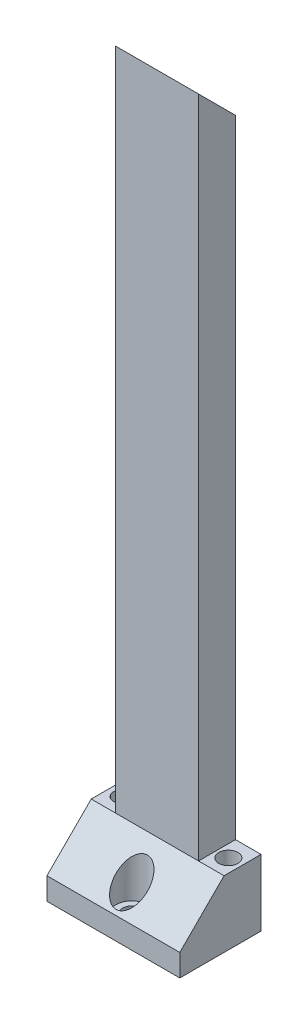
SolidWorks part; units mm, degrees
ref_plane "Front Plane" through (0, 0, 0) normal (0, 0, 1) x (1, 0, 0)
ref_plane "Top Plane" through (0, 0, 0) normal (0, 1, 0) x (1, 0, 0)
ref_plane "Right Plane" through (0, 0, 0) normal (1, 0, 0) x (0, 0, -1)
sketch "Sketch1" plane through (0, 0, 0) normal (0, 1, 0) x (1, 0, 0)
  line L0 (-2, 8.9269) -> (-2, -9.4231) construction
  line L1 (-17, 8.9269) -> (13, 8.9269)
  line L2 (-17, 8.9269) -> (-17, -9.4231)
  line L3 (-17, -9.4231) -> (13, -9.4231)
  line L4 (13, 8.9269) -> (13, -9.4231)
  line L5 (-17, 4.5423) -> (13, 4.5423)
  circle A0 centre (10, 4.5423) radius 2.1584
  circle A1 centre (-14, 4.5423) radius 1.9195
  circle A2 centre (-2, -5.2684) radius 2.1376
  point P9 (-2, 8.9269)
  point P12 (0, 0)
  dimension "D1" = 30
  dimension "D2" = 13
  dimension "D3" = 18.35
  dimension "D4" = 12
  dimension "D5" = 12
  dimension "D6" = 15.5
extrude "Boss-Extrude1" add sketch "Sketch1" along normal blind 15 contours L1 L0 L5 A0 L4 | L0 L1 L2 L5 A1 | L0 L5 A1 L2 L3 A2 | L5 L0 A2 L3 L4 A0 region at (4.9366, 0, -6.8944) region at (-9.0658, 0, -6.8675) region at (5.5738, 0, 2.564) region at (-9.6083, 0, 2.5188)
chamfer "Chamfer1" distance 10 angle 45 1 edges at (-2, 15, 9.4231)
ref_plane "Plane1" through (0, 15, 0) normal (0, 1, 0) x (1, 0, 0)
sketch "Sketch2" plane through (0, 15, 0) normal (0, 1, 0) x (1, 0, 0)
  circle A0 centre (-2, -5.2684) radius 3.5447
extrude "Cut-Extrude1" cut sketch "Sketch2" against normal blind 12
sketch "Sketch3" plane through (0, 15, 0) normal (0, 1, 0) x (1, 0, 0)
  line L0 (7.8416, 4.5423) -> (7.8416, 0.5769) construction
  line L1 (-17, 0.5769) -> (13, 0.5769) construction
  line L2 (-12.0805, 4.5423) -> (-12.0805, 0.5769) construction
  line L3 (-17, 8.9269) -> (13, 8.9269) construction
  line L4 (-11.5265, 0.5769) -> (7.2327, 0.5769)
  line L5 (-11.5265, 0.5769) -> (-11.5265, 8.9269)
  line L6 (-11.5265, 8.9269) -> (7.2327, 8.9269)
  line L7 (7.2327, 0.5769) -> (7.2327, 8.9269)
  circle A0 centre (10, 4.5423) radius 2.1584 construction
  circle A1 centre (-14, 4.5423) radius 1.9195 construction
extrude "Boss-Extrude2" add sketch "Sketch3" along normal blind 150
sketch "Sketch4" plane through (7.2327, 0, 0) normal (1, 0, 0) x (0, 0, -1)
  line L0 (0.5769, 165) -> (8.9269, 156.65)
  line L1 (8.9269, 165) -> (8.9269, 15) construction
  line L2 (8.9269, 156.65) -> (8.9269, 165)
  line L3 (8.9269, 165) -> (0.5769, 165)
extrude "Cut-Extrude2" cut sketch "Sketch4" against normal blind 150
sketch "Sketch5" plane through (0, 82.7885, -82.7885) normal (0, 0.7071, -0.7071) x (1, 0, 0)
  line L1 (3.7365, -112.0212) -> (-8.9793, -112.0212)
  line L2 (3.7365, -112.0212) -> (3.7365, -108.4294)
  line L3 (3.7365, -108.4294) -> (-8.9793, -108.4294)
  line L4 (-8.9793, -112.0212) -> (-8.9793, -108.4294)
extrude "Cut-Extrude3" cut sketch "Sketch5" against normal blind 4
